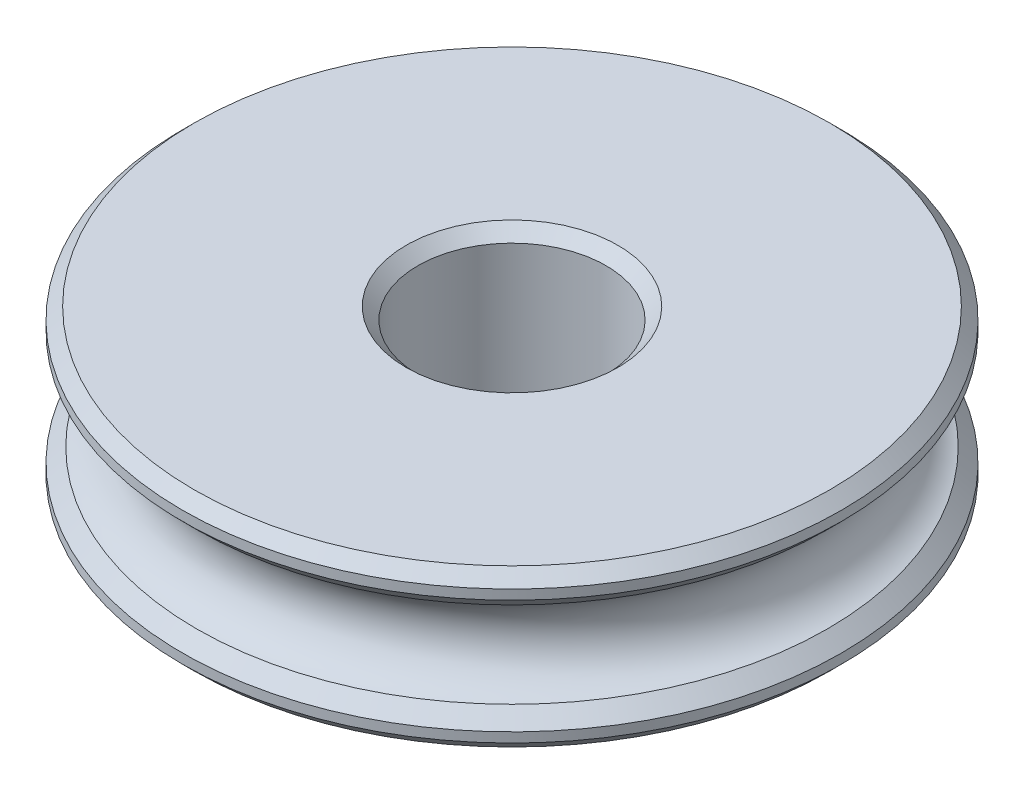
SolidWorks part; units mm, degrees
ref_plane "Front Plane" through (0, 0, 0) normal (0, 0, 1) x (1, 0, 0)
ref_plane "Top Plane" through (0, 0, 0) normal (0, 1, 0) x (1, 0, 0)
ref_plane "Right Plane" through (0, 0, 0) normal (1, 0, 0) x (0, 0, -1)
sketch "Sketch1" plane through (0, 0, 0) normal (0, 1, 0) x (1, 0, 0)
  circle A0 centre (0, 0) radius 42
  circle A1 centre (0, 0) radius 12
extrude "Boss-Extrude1" add sketch "Sketch1" along normal mid plane 20
sketch "Sketch2" plane through (0, 0, 0) normal (0, 0, 1) x (1, 0, 0)
  line L0 (42, -5) -> (42, 5)
  line L3 (42, -5) -> (42, 5) construction
  line L5 (42, 5) -> (42, -5) construction
  arc A1 (42, -5) -> (42, 5) centre (42, 0) cw
  dimension "D2" = 10
sketch "Sketch5" plane through (0, 10, 0) normal (0, 1, 0) x (1, 0, 0)
ref_plane "Plane1" through (0, 0, 0) normal (0, 0, 1) x (1, 0, 0)
sketch "Sketch6" plane through (0, 0, 0) normal (0, 0, 1) x (1, 0, 0)
  line L0 (0, 0) -> (0, 10) construction
  line L1 (42, 10) -> (-42, 10) construction
  line L3 (-42, 5.7646) -> (-42, -5.7646)
  line L4 (-42, 10) -> (-42, -10) construction
  line L9 (0, 10) -> (-42, 10) construction
  arc A0 (-42, 5.7646) -> (-42, -5.7646) centre (-42, 0) cw
  dimension "D2" = 5.7646
sketch "Sketch11" plane through (0, 0, 0) normal (0, 0, 1) x (1, 0, 0)
  line L0 (0, -10) -> (0, 10) construction
  line L1 (-42, -10) -> (42, -10) construction
  line L2 (0, 10) -> (-42, 10) construction
  line L3 (-42, 10) -> (-42, -10) construction
  line L4 (-42, -10) -> (0, -10) construction
revolve "Cut-Revolve11" cut sketch "Sketch6" angle 360 about L0
chamfer "Chamfer1" distance 1.5 angle 45 6 edges at (0, 10, 12) (0, -10, 42) (0, -10, 12) (42, 5.7646, 0) (42, -5.7646, 0) (0, 10, 42)
